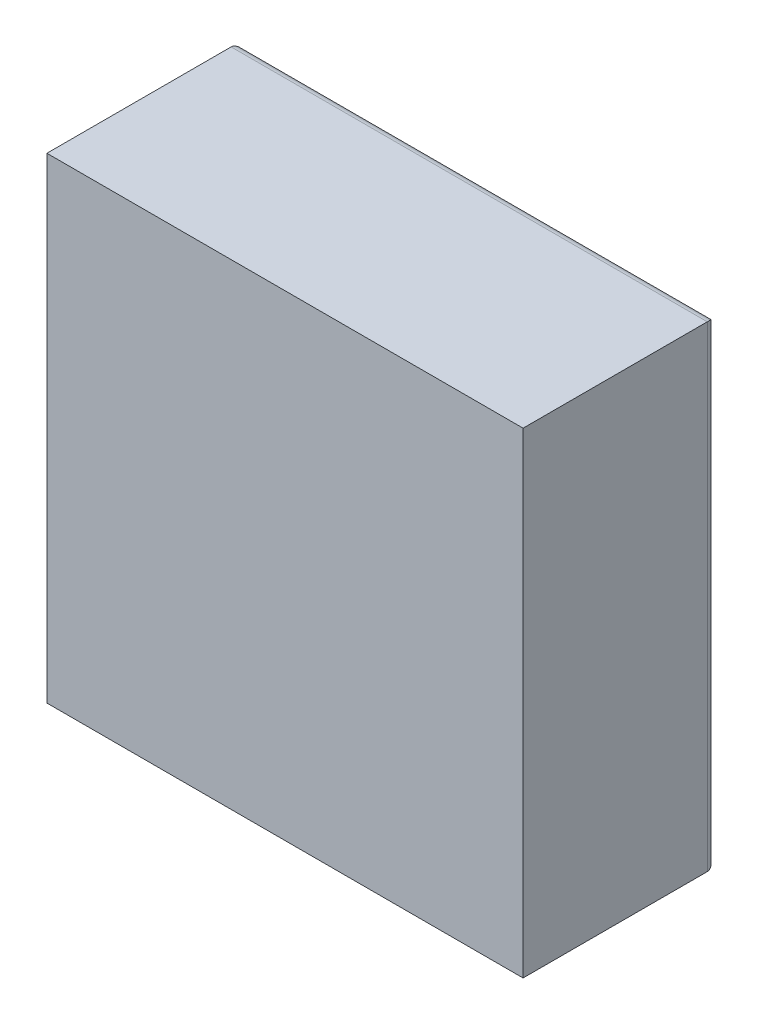
SolidWorks part; units mm, degrees
material "Alumina"
ref_plane "Front Plane" through (0, 0, 0) normal (0, 0, 1) x (1, 0, 0)
ref_plane "Top Plane" through (0, 0, 0) normal (0, 1, 0) x (1, 0, 0)
ref_plane "Right Plane" through (0, 0, 0) normal (1, 0, 0) x (0, 0, -1)
sketch "Sketch1" plane through (0, 0, 0) normal (0, 0, 1) x (1, 0, 0)
  line L1 (252, 252) -> (-252, 252)
  line L2 (252, 252) -> (252, -252)
  line L3 (252, -252) -> (-252, -252)
  line L4 (-252, 252) -> (-252, -252)
  line L5 (252, 252) -> (-252, -252) construction
  line L6 (252, -252) -> (-252, 252) construction
  point P0 (0, 0)
extrude "Boss-Extrude1" add sketch "Sketch1" along normal blind 205
sketch "Sketch2" plane through (0, 0, 0) normal (0, 0, -1) x (-1, 0, 0)
  line L1 (-250, 250) -> (250, 250)
  line L2 (-250, 250) -> (-250, -250)
  line L3 (-250, -250) -> (250, -250)
  line L4 (250, 250) -> (250, -250)
  line L5 (-250, 250) -> (250, -250) construction
  line L6 (-250, -250) -> (250, 250) construction
  point P0 (0, 0)
extrude "Cut-Extrude1" cut sketch "Sketch2" against normal blind 200
fillet "Fillet2" radius 10 5 edges at (0, -252, 0) (252, 0, 0) (0, 252, 0) (-252, 0, 0) (-250, -250, 100)
fillet "Fillet4" radius 10 5 edges at (250, 0, 200) (0, 250, 200) (-250, 5, 200) (-247.0711, -247.0711, 200) (5, -250, 200)
